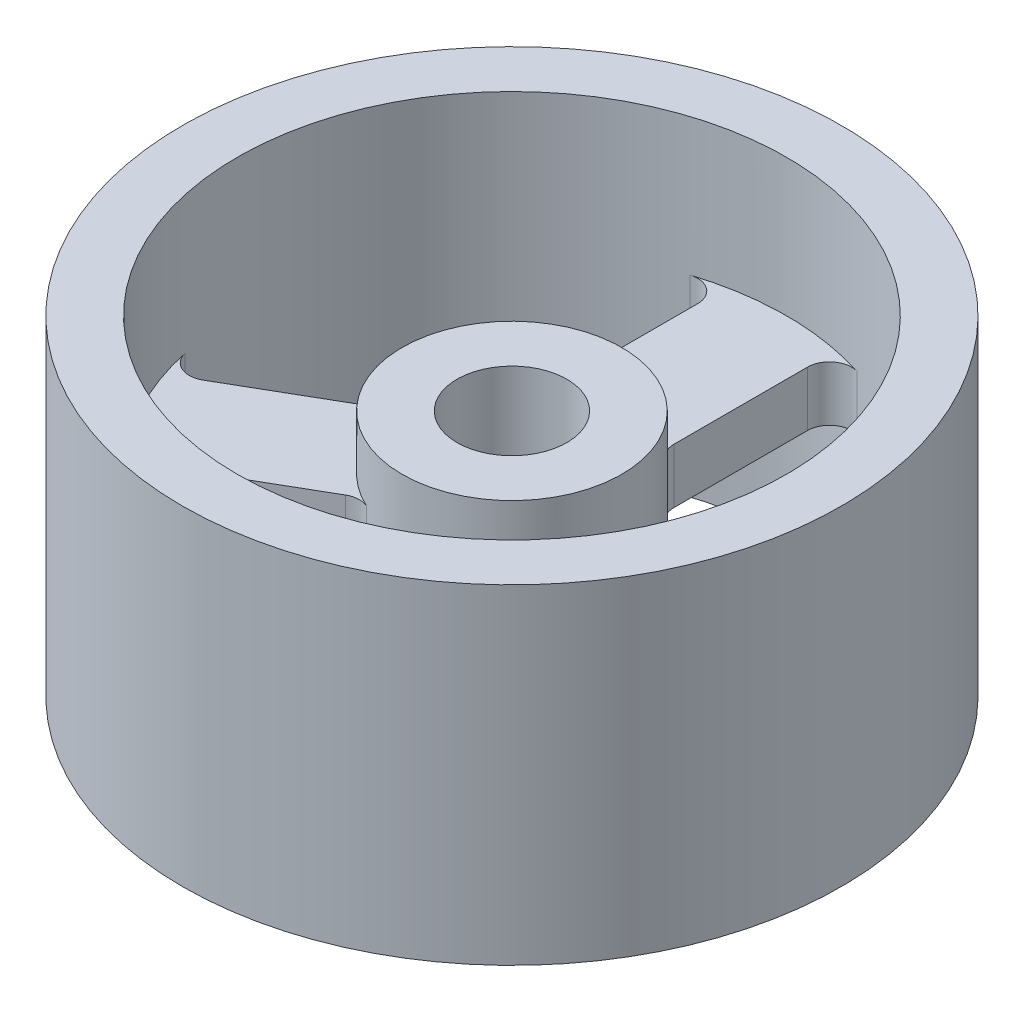
SolidWorks part; units mm, degrees
ref_plane "Front Plane" through (0, 0, 0) normal (0, 0, 1) x (1, 0, 0)
ref_plane "Top Plane" through (0, 0, 0) normal (0, 1, 0) x (1, 0, 0)
ref_plane "Right Plane" through (0, 0, 0) normal (1, 0, 0) x (0, 0, -1)
sketch "Sketch1" plane through (0, 0, 0) normal (0, 1, 0) x (1, 0, 0)
  line L0 (0, 70.7865) -> (0, -63.2381) construction
  line L1 (-115.9663, 0) -> (101.026, 0) construction
  line L2 (0, 0) -> (-21.6506, -12.5) construction
  line L3 (0, 0) -> (21.6506, -12.5) construction
  line L4 (10.941, -0.5433) -> (21.4737, -6.6243)
  line L5 (5.941, -9.2035) -> (16.4737, -15.2846)
  line L6 (-5.941, -9.2035) -> (-16.4737, -15.2846)
  line L7 (-10.941, -0.5433) -> (-21.4737, -6.6243)
  line L8 (-5, 9.7468) -> (-5, 21.9089)
  line L9 (5, 9.7468) -> (5, 21.9089)
  circle A0 centre (0, 0) radius 25
  circle A1 centre (0, 0) radius 30
  circle A2 centre (0, 0) radius 5
  circle A3 centre (0, 0) radius 10
  arc A4 (16.8192, -18.4963) -> (16.4737, -15.2846) centre (15.4737, -17.0166) ccw
  arc A5 (24.4279, -5.3177) -> (21.4737, -6.6243) centre (22.4737, -4.8923) cw
  arc A6 (5.941, -9.2035) -> (4.1175, -9.113) centre (4.941, -10.9356) ccw
  arc A7 (10.941, -0.5433) -> (9.9508, 0.9907) centre (11.941, 1.1888) cw
  arc A8 (-5.941, -9.2035) -> (-4.1175, -9.113) centre (-4.941, -10.9356) cw
  arc A9 (-16.8192, -18.4963) -> (-16.4737, -15.2846) centre (-15.4737, -17.0166) cw
  arc A10 (-24.4279, -5.3177) -> (-21.4737, -6.6243) centre (-22.4737, -4.8923) ccw
  circle A11 centre (0, 0) radius 25
  arc A12 (-10.941, -0.5433) -> (-9.9508, 0.9907) centre (-11.941, 1.1888) ccw
  arc A13 (-5, 9.7468) -> (-5.8333, 8.1223) centre (-7, 9.7468) cw
  arc A14 (-7.6087, 23.814) -> (-5, 21.9089) centre (-7, 21.9089) cw
  arc A15 (7.6087, 23.814) -> (5, 21.9089) centre (7, 21.9089) ccw
  circle A16 centre (0, 0) radius 25
  arc A17 (5, 9.7468) -> (5.8333, 8.1223) centre (7, 9.7468) ccw
  point P53 (0, 0)
  dimension "D1" = 60
  dimension "D2" = 50
  dimension "D3" = 20
  dimension "D4" = 10
  dimension "D6" = 2
  dimension "D8" = 3
  dimension "D5" = 60
  dimension "D7" = 10
extrude "Boss-Extrude1" add sketch "Sketch1" along normal mid plane 30 contours A1 A0 A11 region at (-29.1515, 0, 0)
extrude "Boss-Extrude2" add sketch "Sketch1<3>" along normal mid plane 15 separate body contours A3 A2 region at (9.7052, 0, -0.4819)
sketch "Sketch1<3>" plane through (0, 0, 0) normal (0, 1, 0) x (1, 0, 0) same geometry as "Sketch1"
extrude "Boss-Extrude3" add sketch "Sketch1<4>" along normal mid plane 5 contours A17 L9 A15 A11 A14 L8 A13 A3 | L4 A7 A3 A6 L5 A4 A0 A5 | A12 L7 A10 A0 A9 L6 A8 A3 region at (14.9903, 0, 8.6546) region at (0, 0, -17.3093) region at (-14.9903, 0, 8.6546)
sketch "Sketch1<4>" plane through (0, 0, 0) normal (0, 1, 0) x (1, 0, 0) same geometry as "Sketch1"
